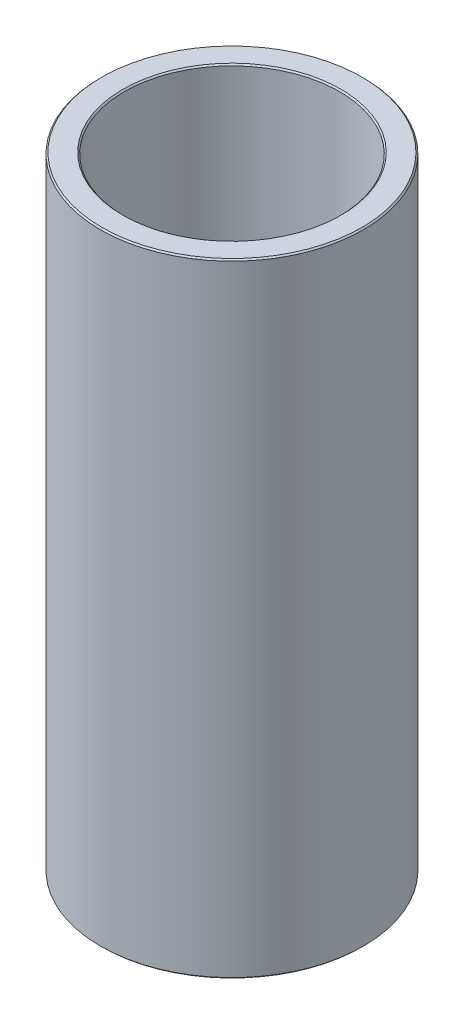
SolidWorks part; units mm, degrees
ref_plane "Front Plane" through (0, 0, 0) normal (0, 0, 1) x (1, 0, 0)
ref_plane "Top Plane" through (0, 0, 0) normal (0, 1, 0) x (1, 0, 0)
ref_plane "Right Plane" through (0, 0, 0) normal (1, 0, 0) x (0, 0, -1)
sketch "Sketch1" plane through (0, 0, 0) normal (0, 1, 0) x (1, 0, 0)
  circle A0 centre (0, 0) radius 55
  dimension "SLEEVE_OD" = 110
extrude "Boss-Extrude1" add sketch "Sketch1" along normal blind 260.6252
sketch "Sketch2" plane through (0, 0, 0) normal (0, 1, 0) x (1, 0, 0)
  circle A0 centre (0, 0) radius 45.0552
  dimension "BORE_D" = 90.1104
extrude "Cut-Extrude1" cut sketch "Sketch2" along normal through all
chamfer "Chamfer1" distance 0.5841 angle 44.653 4 edges at (0, 260.6252, 45.0552) (0, 0, 45.0552) (0, 0, 55) (0, 260.6252, 55) first distance on face at (0, 260.6252, 45.0552) first distance on face at (0, 0, 45.0552) first distance on face at (0, 260.6252, 55)
